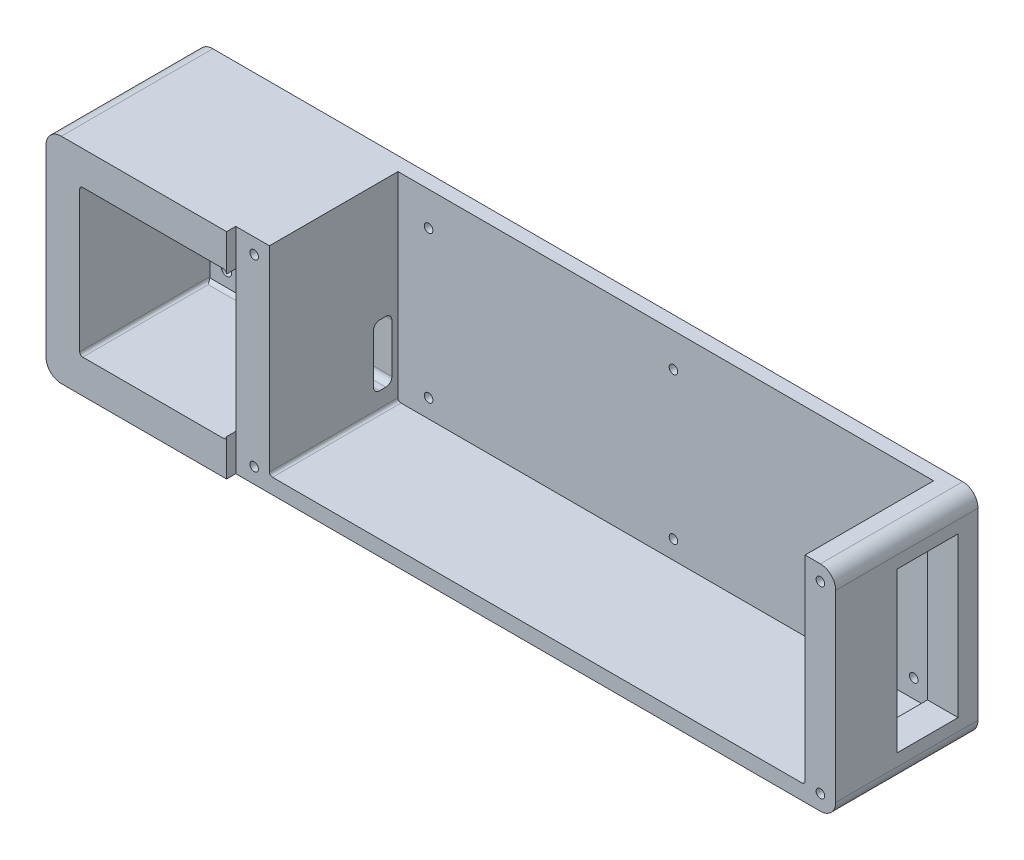
SolidWorks part; units mm, degrees
ref_plane "正面" through (0, 0, 0) normal (0, 0, 1) x (1, 0, 0)
ref_plane "平面" through (0, 0, 0) normal (0, 1, 0) x (1, 0, 0)
ref_plane "右側面" through (0, 0, 0) normal (1, 0, 0) x (0, 0, -1)
sketch "ｽｹｯﾁ1" plane through (0, 0, 0) normal (0, 0, 1) x (1, 0, 0)
  line L1 (0, 0) -> (70, 0)
  line L2 (0, 0) -> (0, 70)
  line L3 (0, 70) -> (70, 70)
  line L4 (70, 0) -> (70, 70)
  line L5 (11, 11) -> (59, 11)
  line L6 (11, 11) -> (11, 59)
  line L7 (11, 59) -> (59, 59)
  line L8 (59, 11) -> (59, 59)
  dimension "D1" = 70
  dimension "D2" = 70
  dimension "D3" = 48
  dimension "D4" = 48
  dimension "D5" = 11
  dimension "D6" = 11
extrude "ﾎﾞｽ - 押し出し1" add sketch "ｽｹｯﾁ1" along normal blind 49.5 contours L6 L5 L8 L7 | L2 L1 L4 L3
sketch "ｽｹｯﾁ2" plane through (0, 0, 0) normal (0, 0, -1) x (-1, 0, 0)
  line L1 (-59, 59) -> (-11, 59)
  line L2 (-59, 59) -> (-59, 11)
  line L3 (-59, 11) -> (-11, 11)
  line L4 (-11, 59) -> (-11, 11)
extrude "ﾎﾞｽ - 押し出し2" add sketch "ｽｹｯﾁ2" against normal blind 7
sketch "ｽｹｯﾁ3" plane through (70, 0, 0) normal (1, 0, 0) x (0, 0, -1)
  line L1 (-12.5, 11) -> (-6.5, 11)
  line L2 (-12.5, 11) -> (-12.5, 31)
  line L3 (-12.5, 31) -> (-6.5, 31)
  line L4 (-6.5, 11) -> (-6.5, 31)
  line L5 (-49.5, 0) -> (-49.5, 70) construction
  line L6 (-49.5, 0) -> (0, 0) construction
  dimension "D1" = 37
  dimension "D2" = 6
  dimension "D3" = 20
  dimension "D4" = 11
extrude "ｶｯﾄ - 押し出し1" cut sketch "ｽｹｯﾁ3" against normal blind 41
sketch "ｽｹｯﾁ4" plane through (70, 0, 0) normal (1, 0, 0) x (0, 0, -1)
  line L0 (-49.5, 0) -> (0, 0) construction
  line L1 (0, 70) -> (-4.5, 70)
  line L2 (0, 70) -> (0, 0)
  line L3 (0, 0) -> (-4.5, 0)
  line L4 (-4.5, 70) -> (-4.5, 0)
  dimension "D1" = 4.5
extrude "ﾎﾞｽ - 押し出し3" add sketch "ｽｹｯﾁ4" along normal blind 180
sketch "ｽｹｯﾁ5" plane through (0, 0, 4.5) normal (0, 0, 1) x (1, 0, 0)
  line L0 (250, 70) -> (250, 0) construction
  line L1 (70, 0) -> (250, 0)
  line L2 (70, 0) -> (70, 5)
  line L3 (70, 5) -> (250, 5)
  line L4 (250, 0) -> (250, 5)
  dimension "D1" = 5
extrude "ﾎﾞｽ - 押し出し4" add sketch "ｽｹｯﾁ5" along normal blind 45
sketch "ｽｹｯﾁ6" plane through (0, 0, 4.5) normal (0, 0, 1) x (1, 0, 0)
  line L0 (250, 5) -> (70, 5) construction
  line L1 (243, 64) -> (165, 64) construction
  line L2 (243, 64) -> (243, 6) construction
  line L3 (243, 6) -> (165, 6) construction
  line L4 (165, 64) -> (165, 6) construction
  line L5 (250, 70) -> (250, 5) construction
  line L7 (76, 63) -> (164, 63) construction
  line L8 (76, 63) -> (76, 7) construction
  line L9 (76, 7) -> (164, 7) construction
  line L10 (164, 63) -> (164, 7) construction
  circle A0 centre (238.5, 59) radius 1.4
  circle A1 centre (238.5, 11) radius 1.4
  circle A2 centre (160, 59) radius 1.4
  circle A3 centre (160, 11) radius 1.4
  circle A4 centre (80, 59) radius 1.4
  circle A5 centre (80, 11) radius 1.4
  dimension "D6" = 2.8
  dimension "D7" = 2.8
  dimension "D15" = 2.8
  dimension "D16" = 2.8
  dimension "D17" = 2.8
  dimension "D18" = 2.8
  dimension "D1" = 58
  dimension "D2" = 78
  dimension "D3" = 1
  dimension "D4" = 7
  dimension "D5" = 48
  dimension "D8" = 5
  dimension "D9" = 4.5
  dimension "D10" = 4.5
  dimension "D11" = 88
  dimension "D12" = 56
  dimension "D13" = 2
  dimension "D14" = 1
  dimension "D19" = 48
  dimension "D20" = 48
  dimension "D21" = 80
  dimension "D22" = 80
  dimension "D23" = 4
  dimension "D24" = 4
  dimension "D25" = 4
  dimension "D26" = 4
extrude "ｶｯﾄ - 押し出し2" cut sketch "ｽｹｯﾁ6" against normal blind 45
sketch "ｽｹｯﾁ7" plane through (0, 0, 4.5) normal (0, 0, 1) x (1, 0, 0)
  line L0 (250, 70) -> (70, 70) construction
  line L1 (250, 5) -> (245, 5)
  line L2 (250, 5) -> (250, 70)
  line L3 (250, 70) -> (245, 70)
  line L4 (245, 5) -> (245, 70)
  dimension "D1" = 5
extrude "ﾎﾞｽ - 押し出し5" add sketch "ｽｹｯﾁ7" along normal blind 45
sketch "ｽｹｯﾁ8" plane through (250, 0, 0) normal (1, 0, 0) x (0, 0, -1)
  line L1 (0, 70) -> (-49.5, 70)
  line L2 (0, 70) -> (0, 0)
  line L3 (0, 0) -> (-49.5, 0)
  line L4 (-49.5, 70) -> (-49.5, 0)
extrude "ﾎﾞｽ - 押し出し6" add sketch "ｽｹｯﾁ8" along normal blind 5
sketch "ｽｹｯﾁ9" plane through (245, 0, 0) normal (-1, 0, 0) x (0, 0, 1)
  line L0 (49.5, 5) -> (4.5, 5) construction
  line L1 (6.5, 9) -> (26.5, 9)
  line L2 (6.5, 9) -> (6.5, 61)
  line L3 (6.5, 61) -> (26.5, 61)
  line L4 (26.5, 9) -> (26.5, 61)
  line L6 (49.5, 70) -> (4.5, 70) construction
  line L8 (4.5, 70) -> (4.5, 5) construction
  dimension "D1" = 9
  dimension "D2" = 20
  dimension "D3" = 4
  dimension "D4" = 2
extrude "ｶｯﾄ - 押し出し3" cut sketch "ｽｹｯﾁ9" against normal blind 10
fillet "ﾌｨﾚｯﾄ3" radius 5 4 edges at (255, 0, 24.75) (255, 70, 24.75) (0, 70, 24.75) (0, 0, 24.75)
fillet "ﾌｨﾚｯﾄ4" radius 1 4 edges at (59, 11, 31) (59, 59, 28.25) (11, 59, 28.25) (11, 11, 28.25)
fillet "ﾌｨﾚｯﾄ5" radius 2 4 edges at (64, 11, 12.5) (64.5, 31, 12.5) (49.5, 11, 6.5) (49.5, 31, 6.5)
fillet "ﾌｨﾚｯﾄ6" radius 2 2 edges at (44, 30.3229, 7) (29, 21, 7)
fillet "ﾌｨﾚｯﾄ7" radius 2 6 edges at (59, 12.4824, 12.4319) (58.6726, 11.26, 11.4861) (59, 30.7229, 7.4842) (59, 30.4142, 11.9142) (59, 31, 9.5) (59, 21, 12.5)
fillet "ﾌｨﾚｯﾄ8" radius 1 2 edges at (245, 5, 27) (70, 5, 27)
sketch "ｽｹｯﾁ10" plane through (0, 0, 7) normal (0, 0, 1) x (1, 0, 0)
  line L3 (12, 11) -> (58, 11) construction
  line L4 (11, 12) -> (11, 58) construction
  line L6 (59, 58) -> (59, 32.7081) construction
  circle A0 centre (16.5, 53.5) radius 1.65
  circle A1 centre (16.5, 16.5) radius 1.65
  circle A2 centre (53.5, 53.5) radius 1.65
  dimension "D3" = 3.3
  dimension "D4" = 3.3
  dimension "D5" = 3.3
  dimension "D1" = 37
  dimension "D2" = 37
  dimension "D6" = 5.5
  dimension "D7" = 5.5
  dimension "D8" = 5.5
  dimension "D9" = 5.5
extrude "ｶｯﾄ - 押し出し4" cut sketch "ｽｹｯﾁ10" against normal through all
sketch "ｽｹｯﾁ11" plane through (0, 0, 49.5) normal (0, 0, 1) x (1, 0, 0)
  line L0 (70, 70) -> (70, 6) construction
  line L1 (5, 70) -> (70, 70) construction
  line L2 (5, 0) -> (250, 0) construction
  line L3 (255, 65) -> (255, 5) construction
  circle A0 centre (65, 65) radius 1.4
  circle A1 centre (65, 5) radius 1.4
  circle A2 centre (250, 65) radius 1.4
  circle A3 centre (250, 5) radius 1.4
  dimension "D3" = 2.8
  dimension "D4" = 2.8
  dimension "D5" = 2.8
  dimension "D6" = 2.8
  dimension "D1" = 60
  dimension "D2" = 60
  dimension "D7" = 185
  dimension "D8" = 185
  dimension "D9" = 5
  dimension "D10" = 5
  dimension "D11" = 5
  dimension "D12" = 5
extrude "ｶｯﾄ - 押し出し5" cut sketch "ｽｹｯﾁ11" against normal blind 15
ref_plane "平面2" through (5, 0, 49.5) normal (1, 0, 0) x (0, 0, -1)
sketch "ｽｹｯﾁ13" plane through (0, 0, 49.5) normal (0, 0, 1) x (1, 0, 0)
  line L0 (5, 0) -> (250, 0) construction
  line L1 (59, 0) -> (255, 0)
  line L2 (59, 0) -> (59, 70)
  line L3 (59, 70) -> (255, 70)
  line L4 (255, 0) -> (255, 70)
  line L5 (59, 12) -> (59, 58) construction
  line L6 (255, 65) -> (255, 5) construction
  line L7 (250, 70) -> (245, 70) construction
extrude "ｶｯﾄ - 押し出し6" cut sketch "ｽｹｯﾁ13" against normal blind 3
